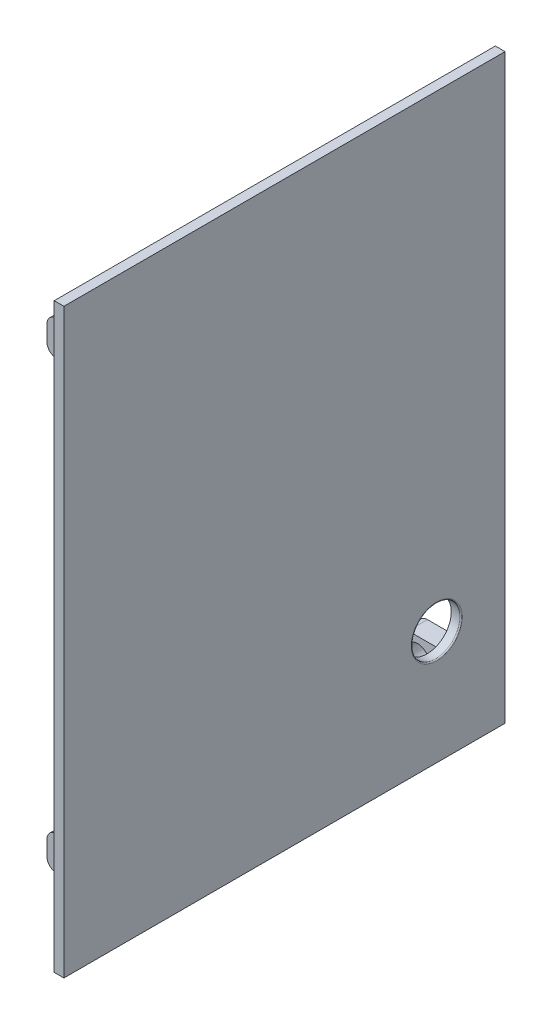
SolidWorks part; units mm, degrees
ref_plane "Front Plane" through (0, 0, 0) normal (0, 0, 1) x (1, 0, 0)
ref_plane "Top Plane" through (0, 0, 0) normal (0, 1, 0) x (1, 0, 0)
ref_plane "Right Plane" through (0, 0, 0) normal (1, 0, 0) x (0, 0, -1)
ref_plane "Plane1" through (282.5307, 0, 0) normal (1, 0, 0) x (0, 0, -1)
sketch "Sketch3" plane through (282.5307, 0, 0) normal (1, 0, 0) x (0, 0, -1)
  line L1 (-32.2372, 19.7391) -> (58.7628, 19.7391)
  line L2 (-32.2372, 19.7391) -> (-32.2372, 139.7391)
  line L3 (-32.2372, 139.7391) -> (58.7628, 139.7391)
  line L4 (58.7628, 19.7391) -> (58.7628, 139.7391)
extrude "Boss-Extrude1" add sketch "Sketch3" along normal blind 2
sketch "Sketch4" plane through (284.5307, 0, 0) normal (1, 0, 0) x (0, 0, -1)
  circle A0 centre (44.6678, 43.1891) radius 5
  ellipse E0 centre (44.6678, 43.1891) end of major axis (42.4404, 40.9618) minor radius 3.15 construction
  ellipse E1 centre (44.6678, 43.1891) end of major axis (42.4404, 40.9618) minor radius 3.15 construction
  dimension "D1" = 10
extrude "Cut-Extrude1" cut sketch "Sketch4" against normal through all
fillet "Fillet1" radius 0.25 1 edges at (284.5307, 43.1891, -49.6678)
sketch "Sketch5" plane through (282.5307, 0, 0) normal (-1, 0, 0) x (0, 0, 1)
  line L0 (-51.2528, 32.1391) -> (-51.2528, 35.3391) construction
  line L1 (-51.2528, 32.1391) -> (-51.2528, 35.3391)
  line L2 (29.7372, 22.2391) -> (29.7372, 137.2391) construction
  line L3 (-51.7528, 37.2756) -> (-47.7528, 37.2756)
  line L4 (-51.7528, 37.2756) -> (-51.7528, 30.2027)
  line L5 (-51.7528, 30.2027) -> (-47.7528, 30.2027)
  line L6 (-47.7528, 37.2756) -> (-47.7528, 30.2027)
  line L7 (-51.2528, 124.1391) -> (-51.2528, 127.3391) construction
  line L8 (-51.2528, 124.1391) -> (-51.2528, 127.3391)
  line L9 (-56.2628, 137.2391) -> (-56.2628, 125.7391) construction
  line L10 (-52.2528, 122.1391) -> (-48.2528, 122.1391)
  line L11 (-52.2528, 122.1391) -> (-52.2528, 129.3391)
  line L12 (-52.2528, 129.3391) -> (-48.2528, 129.3391)
  line L13 (-48.2528, 122.1391) -> (-48.2528, 129.3391)
  line L14 (24.7372, 30.2027) -> (20.7372, 30.2027)
  line L15 (24.7372, 30.2027) -> (24.7372, 37.2756)
  line L16 (24.7372, 37.2756) -> (20.7372, 37.2756)
  line L17 (20.7372, 30.2027) -> (20.7372, 37.2756)
  line L19 (24.7372, 129.3391) -> (20.7372, 129.3391)
  line L20 (24.7372, 129.3391) -> (24.7372, 122.1391)
  line L21 (24.7372, 122.1391) -> (20.7372, 122.1391)
  line L22 (20.7372, 129.3391) -> (20.7372, 122.1391)
  dimension "D1" = 4
  dimension "D2" = 2
  dimension "D3" = 2
  dimension "D4" = 2
  dimension "D5" = 2
  dimension "D6" = 4
  dimension "D7" = 4.51
  dimension "D8" = 4
  dimension "D9" = 5
  dimension "D10" = 4
  dimension "D11" = 5
extrude "Boss-Extrude2" add sketch "Sketch5" along normal blind 9 contours L10 L13 L12 L11 L8 | L6 L3 L4 L1 L5 | L20 L19 L22 L21 | L15 L14 L17 L16 region at (282.5307, 33.7391, -49.7528) region at (282.5307, 125.7391, -50.2528)
sketch "Sketch6" plane through (0, 0, -48.2528) normal (0, 0, 1) x (1, 0, 0)
  circle A0 centre (277.5307, 33.7391) radius 1.6 construction
  circle A1 centre (277.5307, 125.7391) radius 1.6 construction
  circle A2 centre (277.5307, 33.7391) radius 1.6 construction
  circle A3 centre (277.5307, 125.7391) radius 1.6 construction
  circle A4 centre (277.5307, 33.7391) radius 2.25
  circle A5 centre (277.5307, 125.7391) radius 2.25
  dimension "D1" = 4.5
  dimension "D2" = 4.5
extrude "Cut-Extrude2" cut sketch "Sketch6" against normal through all and the other way through all
fillet "Fillet2" radius 2 8 edges at (273.5307, 129.3391, -50.2528) (273.5307, 122.1391, -50.2528) (273.5307, 129.3391, 22.7372) (273.5307, 122.1391, 22.7372) (273.5307, 37.2756, 22.7372) (273.5307, 30.2027, 22.7372) (273.5307, 37.2756, -49.7528) (273.5307, 30.2027, -49.7528)
equation "\"R_HEATINSERT_BACK\"=4.5"
equation "\"D1@Sketch6\"=\"R_HEATINSERT_BACK\""
equation "\"D2@Sketch6\"=\"R_HEATINSERT_BACK\""
